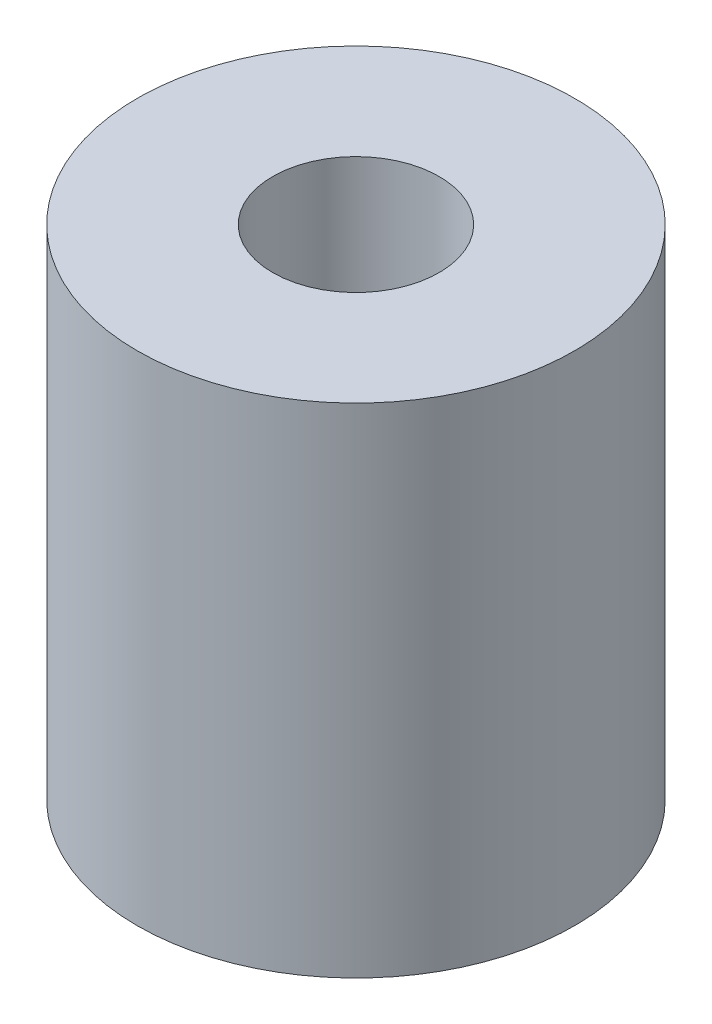
SolidWorks part; units mm, degrees
ref_plane "Front Plane" through (0, 0, 0) normal (0, 0, 1) x (1, 0, 0)
ref_plane "Top Plane" through (0, 0, 0) normal (0, 1, 0) x (1, 0, 0)
ref_plane "Right Plane" through (0, 0, 0) normal (1, 0, 0) x (0, 0, -1)
sketch "Sketch1" plane through (0, 0, 0) normal (0, 1, 0) x (1, 0, 0)
  circle A0 centre (0, 0) radius 13
  circle A1 centre (0, 0) radius 4.95
  dimension "D1" = 26
  dimension "D2" = 9.9
extrude "Boss-Extrude1" add sketch "Sketch1" along normal blind 29.6
ref_plane "Plane1" through (0, 18.6506, 0) normal (0, 1, 0) x (1, 0, 0)
sketch "Sketch2" plane through (0, 18.6506, 0) normal (0, 1, 0) x (1, 0, 0)
  circle A0 centre (0, 0) radius 4.95
extrude "Boss-Extrude3" add sketch "Sketch2" against normal offset from surface (8.6506 mm away) 10 up to face at (0, 0, 13)
sketch "Sketch3" plane through (0, 0, 0) normal (0, -1, 0) x (1, 0, 0)
  circle A1 centre (0, 0) radius 13
  circle A2 centre (0, 0) radius 13
  circle A3 centre (0, 0) radius 3.9
  circle A4 centre (0, 0) radius 4.95 construction
  circle A5 centre (0, 0) radius 4.95
  circle M5 centre (0, 0) radius 4.95
  dimension "D2" = 7.8
  dimension "D1" = 0
extrude "Boss-Extrude4" add sketch "Sketch3" against normal blind 11.85 contours A3 M5 region at (-4.81, 0, 0)
